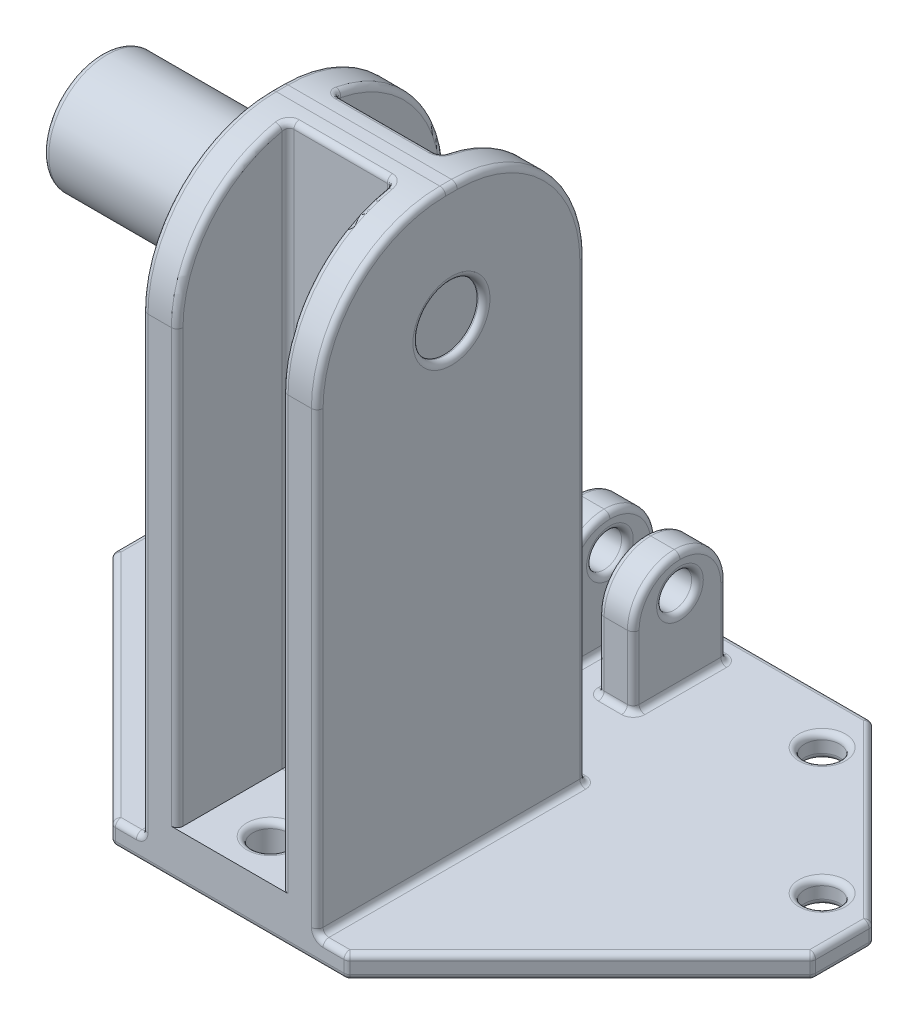
SolidWorks part; units mm, degrees
ref_plane "Front Plane" through (0, 0, 0) normal (0, 0, 1) x (1, 0, 0)
ref_plane "Top Plane" through (0, 0, 0) normal (0, 1, 0) x (1, 0, 0)
ref_plane "Right Plane" through (0, 0, 0) normal (1, 0, 0) x (0, 0, -1)
sketch "Sketch1" plane through (0, 0, 0) normal (0, 1, 0) x (1, 0, 0)
  line L0 (-30, -12.5) -> (-30, 12.5)
  line L1 (-30, 12.5) -> (-15, 27.5)
  line L2 (-15, 27.5) -> (15, 27.5)
  line L3 (15, 27.5) -> (30, 12.5)
  line L4 (30, 12.5) -> (30, -12.5)
  line L5 (30, -12.5) -> (-30, -12.5)
  point P3 (0, -12.5)
  point P8 (0, 27.5)
  point P10 (30, 0)
  dimension "D1" = 45
  dimension "D2" = 60
  dimension "D3" = 25
  dimension "D4" = 15
extrude "Boss-Extrude1" add sketch "Sketch1" along normal blind 2
sketch "Sketch2" plane through (0, 2, 0) normal (0, 1, 0) x (1, 0, 0)
  line L0 (0, 0) -> (0, 27.5) construction
  line L1 (15, 27.5) -> (-15, 27.5) construction
  line L2 (0, 38.2574) -> (-41.2957, -3.0384) construction
  line L3 (0, 38.2574) -> (44.8535, -6.5961) construction
  line L4 (-15, 27.5) -> (-30, 12.5) construction
  line L5 (30, 12.5) -> (15, 27.5) construction
  circle A0 centre (-15.0301, 23.2273) radius 1.5
  circle A1 centre (-25.8488, 12.4086) radius 1.5
  circle A2 centre (15.0301, 23.2273) radius 1.5
  circle A3 centre (25.8488, 12.4086) radius 1.5
  dimension "D2" = 3
  dimension "D3" = 21.2557
  dimension "D1" = 3
  dimension "D4" = 15.3
extrude "Cut-Extrude1" cut sketch "Sketch2" against normal through all
sketch "Sketch3" plane through (0, 2, 0) normal (0, 1, 0) x (1, 0, 0)
  line L0 (0, 0) -> (0, 27.5) construction
  line L1 (15, 27.5) -> (-15, 27.5) construction
  line L3 (-4.5, 17.5764) -> (-1.5, 17.5764)
  line L4 (-4.5, 17.5764) -> (-4.5, 25.5764)
  line L5 (-4.5, 25.5764) -> (-1.5, 25.5764)
  line L6 (-1.5, 17.5764) -> (-1.5, 25.5764)
  line L7 (-4.5, 17.5764) -> (-1.5, 25.5764) construction
  line L8 (-4.5, 25.5764) -> (-1.5, 17.5764) construction
  point P5 (-3, 21.5764)
  dimension "D1" = 3
  dimension "D2" = 8
  dimension "D3" = 1.5
extrude "Boss-Extrude2" add sketch "Sketch3" along normal blind 10
sketch "Sketch4" plane through (-4.5, 0, 0) normal (-1, 0, 0) x (0, 0, 1)
  line L0 (-25.5764, 12) -> (-17.5764, 12) construction
  circle A0 centre (-21.5764, 9) radius 1.5
  point P5 (-21.5764, 12)
  dimension "D2" = 3
  dimension "D1" = 3
extrude "Cut-Extrude2" cut sketch "Sketch4" against normal through all
fillet "Fillet1" radius 4 2 edges at (-3, 12, -17.5764) (-3, 12, -25.5764)
mirror "Mirror2" about plane through (0, 0, 0) normal (1, 0, 0) of "Cut-Extrude2", "Fillet1", "Boss-Extrude2"
sketch "Sketch6" plane through (0, 2, 0) normal (0, 1, 0) x (1, 0, 0)
  line L0 (-30, -12.5) -> (30, -12.5) construction
  line L1 (7.5, 10.5) -> (-7.5, 10.5)
  line L2 (7.5, 10.5) -> (7.5, -12.5)
  line L3 (7.5, -12.5) -> (-7.5, -12.5)
  line L4 (-7.5, 10.5) -> (-7.5, -12.5)
  line L5 (7.5, 10.5) -> (-7.5, -12.5) construction
  line L6 (7.5, -12.5) -> (-7.5, 10.5) construction
  point P0 (0, -1)
  point P8 (0, -12.5)
  dimension "D1" = 23
  dimension "D2" = 15
extrude "Boss-Extrude4" add sketch "Sketch6" along normal blind 50
ref_plane "Plane1" through (0, 0, 1) normal (0, 0, 1) x (1, 0, 0)
sketch "Sketch7" plane through (-7.5, 0, 0) normal (-1, 0, 0) x (0, 0, 1)
  circle A0 centre (1, 42) radius 5
  dimension "D1" = 10
extrude "Boss-Extrude5" add sketch "Sketch7" along normal blind 15
fillet "Fillet2" radius 11 2 edges at (0, 52, -10.5) (0, 52, 12.5)
sketch "Sketch9" plane through (7.5, 0, 0) normal (1, 0, 0) x (0, 0, -1)
  circle A0 centre (-1, 42) radius 2.8
  dimension "D1" = 5.6
extrude "Cut-Extrude4" cut sketch "Sketch9" against normal blind 0.6
chamfer "Chamfer1" distance 20 angle 45 2 edges at (30, 1, 12.5) (-30, 1, 12.5)
ref_plane "Plane2" through (0, 4, 0) normal (0, 1, 0) x (1, 0, 0)
sketch "Sketch8" plane through (0, 4, 0) normal (0, 1, 0) x (1, 0, 0)
  line L0 (7.5, 10.5) -> (-7.5, 10.5) construction
  line L1 (4.5, 10.5) -> (-4.5, 10.5)
  line L2 (4.5, 10.5) -> (4.5, 1)
  line L3 (4.5, 1) -> (-4.5, 1)
  line L4 (-4.5, 10.5) -> (-4.5, 1)
  line L6 (-7.5, 10.5) -> (-7.5, -12.5) construction
  line L7 (7.5, -0.5) -> (7.5, 10.5) construction
  line L8 (-28.6, -1) -> (28.6, -1) construction
  line L9 (7.5, -12.5) -> (-7.5, -12.5) construction
  line L10 (-4.5, -12.5) -> (4.5, -12.5)
  line L11 (-4.5, -12.5) -> (-4.5, -3)
  line L12 (-4.5, -3) -> (4.5, -3)
  line L13 (4.5, -12.5) -> (4.5, -3)
  dimension "D1" = 2
  dimension "D2" = 3
  dimension "D3" = 3
  dimension "D4" = 2
extrude "Cut-Extrude3" cut sketch "Sketch8" along normal through all
sketch "Sketch11" plane through (0, 0, 0) normal (0, -1, 0) x (1, 0, 0)
  circle A0 centre (0, 9.0041) radius 1.52
extrude "Cut-Extrude5" cut sketch "Sketch11" against normal through all contours A0
fillet "Fillet3" radius 0.5 95 edges at (4.5, 22.5, -10.5) (-4.5, 22.5, -10.5) (-4.5, 22.5, 12.5) (4.5, 22.5, 12.5) (4.5, 48.2284, -7.7916) (-4.5, 48.2284, -7.7916) (-4.5, 48.2284, 9.7916) (4.5, 48.2284, 9.7916) (1.5, 5, -25.5764) (1.5, 10.8284, -24.4049) (1.5, 10.8284, -18.748) (1.5, 5, -17.5764) (1.5, 9, -20.0764) (-1.5, 5, -25.5764) (-1.5, 5, -17.5764) (-1.5, 10.8284, -18.748) (-1.5, 10.8284, -24.4049) (-1.5, 9, -20.0764) (4.5, 5, -25.5764) (4.5, 5, -17.5764) (4.5, 10.8284, -18.748) (4.5, 10.8284, -24.4049) (4.5, 9, -20.0764) (-4.5, 5, -25.5764) (-4.5, 10.8284, -24.4049) (-4.5, 10.8284, -18.748) (-4.5, 5, -17.5764) (-4.5, 9, -20.0764) (0, 51.8972, -1) (-4.5, 27.9486, -1) (0, 4, -1) (4.5, 27.9486, -1) (0, 51.8972, 3) (4.5, 27.9486, 3) (0, 4, 3) (-4.5, 27.9486, 3) (-22.5, 42, 6) (-7.5, 21.5, 12.5) (-7.5, 21.5, -10.5) (-7.5, 48.7782, -7.2782) (-7.5, 48.7782, 9.2782) (-7.5, 42, -4) (7.5, 21.5, 12.5) (7.5, 48.7782, 9.2782) (7.5, 48.7782, -7.2782) (7.5, 21.5, -10.5) (15, 1, -27.5) (-15, 1, -27.5) (30, 1, -12.5) (30, 1, -7.5) (22.5, 0, -20) (0, 0, -27.5) (-22.5, 0, -20) (-30, 0, -10) (-20, 0, 2.5) (0, 0, 12.5) (20, 0, 2.5) (30, 0, -10) (-15.0301, 0, -21.7273) (-25.8488, 0, -10.9086) (15.0301, 0, -21.7273) (25.8488, 0, -10.9086) (7.5, 2, 1) (0, 2, -10.5) (-7.5, 2, 1) (-8.75, 2, 12.5) (-20, 2, 2.5) (-30, 2, -10) (-22.5, 2, -20) (0, 2, -27.5) (22.5, 2, -20) (30, 2, -10) (20, 2, 2.5) (8.75, 2, 12.5) (4.5, 2, -21.5764) (3, 2, -25.5764) (1.5, 2, -21.5764) (3, 2, -17.5764) (-15.0301, 2, -21.7273) (-25.8488, 2, -10.9086) (15.0301, 2, -21.7273) (25.8488, 2, -10.9086) (-3, 2, -25.5764) (-4.5, 2, -21.5764) (-3, 2, -17.5764) (-1.5, 2, -21.5764) (10, 1, 12.5) (-10, 1, 12.5) (-30, 1, -7.5) (-30, 1, -12.5) (-7.5, 52, 1) (7.5, 52, 1) (7.5, 42, -1.8) (0, 0, 7.4841) (0, 4, 7.4841)
